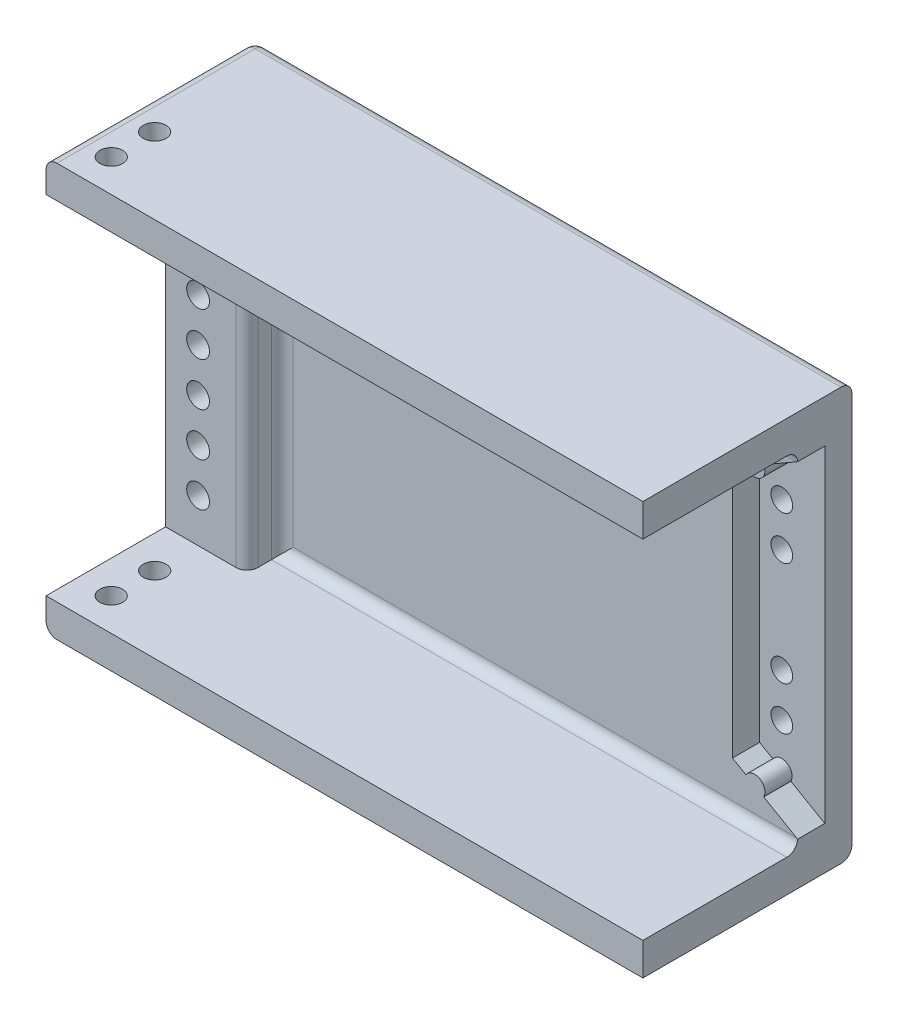
SolidWorks part; units mm, degrees
material "ABS"
ref_plane "前基準面" through (0, 0, 0) normal (0, 0, 1) x (1, 0, 0)
ref_plane "上基準面" through (0, 0, 0) normal (0, 1, 0) x (1, 0, 0)
ref_plane "右基準面" through (0, 0, 0) normal (1, 0, 0) x (0, 0, -1)
sketch "草圖2" plane through (0, 0, 0) normal (0, 0, 1) x (1, 0, 0)
  line L1 (-42.4346, 62.0442) -> (67.4854, 62.0442)
  line L2 (-42.4346, 62.0442) -> (-42.4346, -13.9558)
  line L3 (-42.4346, -13.9558) -> (67.4854, -13.9558)
  line L4 (67.4854, 62.0442) -> (67.4854, -13.9558)
  dimension "D1" = 109.92
  dimension "D2" = 76
extrude "填料-伸長1" add sketch "草圖2" along normal blind 10
sketch "草圖3" plane through (0, 0, 10) normal (0, 0, 1) x (1, 0, 0)
  line L0 (67.4854, 54.1442) -> (67.4854, -6.0558)
  line L1 (67.4854, -13.9558) -> (67.4854, 62.0442) construction
  line L2 (67.4854, 62.0442) -> (-42.4346, 62.0442) construction
  line L3 (67.4854, 54.1442) -> (55.4854, 47.2142)
  line L4 (55.4854, 47.2142) -> (55.4854, 0.8742)
  line L5 (55.4854, 0.8742) -> (67.4854, -6.0558)
  circle A0 centre (59.5654, 49.6442) radius 1.9
  circle A1 centre (59.5654, -1.5558) radius 1.9
  line M6 (67.4854, -13.9558) -> (67.4854, 62.0442)
  dimension "D7" = 7.92
  dimension "D8" = 7.92
  dimension "D9" = 3.8
  dimension "D10" = 3.8
  dimension "D12" = 12.4
  dimension "D1" = 60.2
  dimension "D2" = 7.9
  dimension "D3" = 12
  dimension "D4" = 12
  dimension "D5" = 46.34
  dimension "D6" = 6.93
  dimension "D11" = 51.2
extrude "除料-伸長1" cut sketch "草圖3" against normal blind 5 contours A1 L5 L3 A0 L4 M6 region at (61.776, 24.0442, 10)
sketch "草圖4" plane through (0, 0, 5) normal (0, 0, 1) x (1, 0, 0)
  line L0 (67.4854, -6.0558) -> (67.4854, 54.1442) construction
  circle A0 centre (59.5654, 41.6442) radius 2
  arc A1 (57.953, 48.6392) -> (61.2418, 50.5385) centre (59.5654, 49.6442) ccw construction
  circle A2 centre (59.5654, 33.6442) radius 2
  circle A3 centre (59.5654, 6.4442) radius 2
  arc A4 (61.2418, -2.4501) -> (57.953, -0.5508) centre (59.5654, -1.5558) ccw construction
  circle A5 centre (59.5654, 14.4442) radius 2
  dimension "D1" = 7.92
  dimension "D2" = 8
  dimension "D3" = 4
  dimension "D5" = 4
  dimension "D6" = 7.92
  dimension "D7" = 8
  dimension "D4" = 2
  dimension "D8" = 2
extrude "除料-伸長2" cut sketch "草圖4" against normal through all
sketch "草圖5" plane through (0, 0, 10) normal (0, 0, 1) x (1, 0, 0)
  line L0 (67.4854, -13.9558) -> (67.4854, -6.0558) construction
  line L1 (-42.4346, -13.9558) -> (67.4854, -13.9558)
  line L2 (-42.4346, -13.9558) -> (-42.4346, -7.9558)
  line L3 (-42.4346, -7.9558) -> (67.4854, -7.9558)
  line L4 (67.4854, -13.9558) -> (67.4854, -7.9558)
  line L5 (-42.4346, 62.0442) -> (-42.4346, -13.9558) construction
  line L6 (67.4854, 62.0442) -> (-42.4346, 62.0442)
  line L7 (67.4854, 62.0442) -> (67.4854, 56.0442)
  line L8 (67.4854, 56.0442) -> (-42.4346, 56.0442)
  line L9 (-42.4346, 62.0442) -> (-42.4346, 56.0442)
  dimension "D1" = 6
  dimension "D2" = 6
extrude "填料-伸長2" add sketch "草圖5" along normal blind 28.5
sketch "草圖6" plane through (0, 0, 10) normal (0, 0, 1) x (1, 0, 0)
  line L0 (67.4854, -7.9558) -> (-42.4346, -7.9558) construction
  line L1 (-42.4346, 56.0442) -> (-27.4346, 56.0442)
  line L2 (-42.4346, 56.0442) -> (-42.4346, -7.9558)
  line L3 (-42.4346, -7.9558) -> (-27.4346, -7.9558)
  line L4 (-27.4346, 56.0442) -> (-27.4346, -7.9558)
  dimension "D1" = 15
extrude "填料-伸長3" add sketch "草圖6" along normal blind 6.5
sketch "草圖7" plane through (0, -7.9558, 0) normal (0, 1, 0) x (1, 0, 0)
  line L0 (67.4854, -10) -> (-27.4346, -10) construction
  line L1 (-42.4346, -38.5) -> (-42.4346, -16.5) construction
  circle A0 centre (-36.4346, -24.5) radius 2.1
  circle A1 centre (-36.4346, -32.5) radius 2.1
  dimension "D1" = 4.2
  dimension "D2" = 14.5
  dimension "D4" = 6
  dimension "D3" = 2
extrude "除料-伸長3" cut sketch "草圖7" against normal through all both and the other way through all
sketch "草圖9" plane through (0, 0, 16.5) normal (0, 0, 1) x (1, 0, 0)
  line L0 (-42.4346, 56.0442) -> (-42.4346, -7.9558) construction
  line L1 (-42.4346, -7.9558) -> (-27.4346, -7.9558) construction
  circle A0 centre (-36.4346, 0.0442) radius 2.1
  circle A1 centre (-36.4346, 8.0442) radius 2.1
  circle A2 centre (-36.4346, 16.0442) radius 2.1
  circle A3 centre (-36.4346, 24.0442) radius 2.1
  circle A4 centre (-36.4346, 32.0442) radius 2.1
  circle A5 centre (-36.4346, 40.0442) radius 2.1
  circle A6 centre (-36.4346, 48.0442) radius 2.1
  dimension "D1" = 6
  dimension "D2" = 4.2
  dimension "D3" = 8
  dimension "D4" = 7
extrude "除料-伸長4" cut sketch "草圖9" against normal through all
sketch "草圖10" plane through (0, 0, 0) normal (0, 0, -1) x (-1, 0, 0)
  line L0 (36.4346, 0.0442) -> (36.4346, 48.0442) construction
  line L1 (32.4346, 0.0442) -> (32.4346, 48.0442)
  line L2 (40.4346, 0.0442) -> (40.4346, 48.0442)
  arc A0 (32.4346, 0.0442) -> (40.4346, 0.0442) centre (36.4346, 0.0442) ccw
  arc A1 (40.4346, 48.0442) -> (32.4346, 48.0442) centre (36.4346, 48.0442) ccw
  point P4 (36.4346, 24.0442)
  dimension "D1" = 8
extrude "除料-伸長5" cut sketch "草圖10" against normal blind 5
fillet "圓角1" radius 2 9 edges at (-27.4346, 24.0442, 16.5) (-27.4346, 24.0442, 10) (20.0254, 56.0442, 10) (20.0254, -7.9558, 10) (-42.4346, 62.0442, 19.25) (-42.4346, -13.9558, 19.25) (-42.4346, 24.0442, 0) (12.5254, -13.9558, 0) (12.5254, 62.0442, 0)
